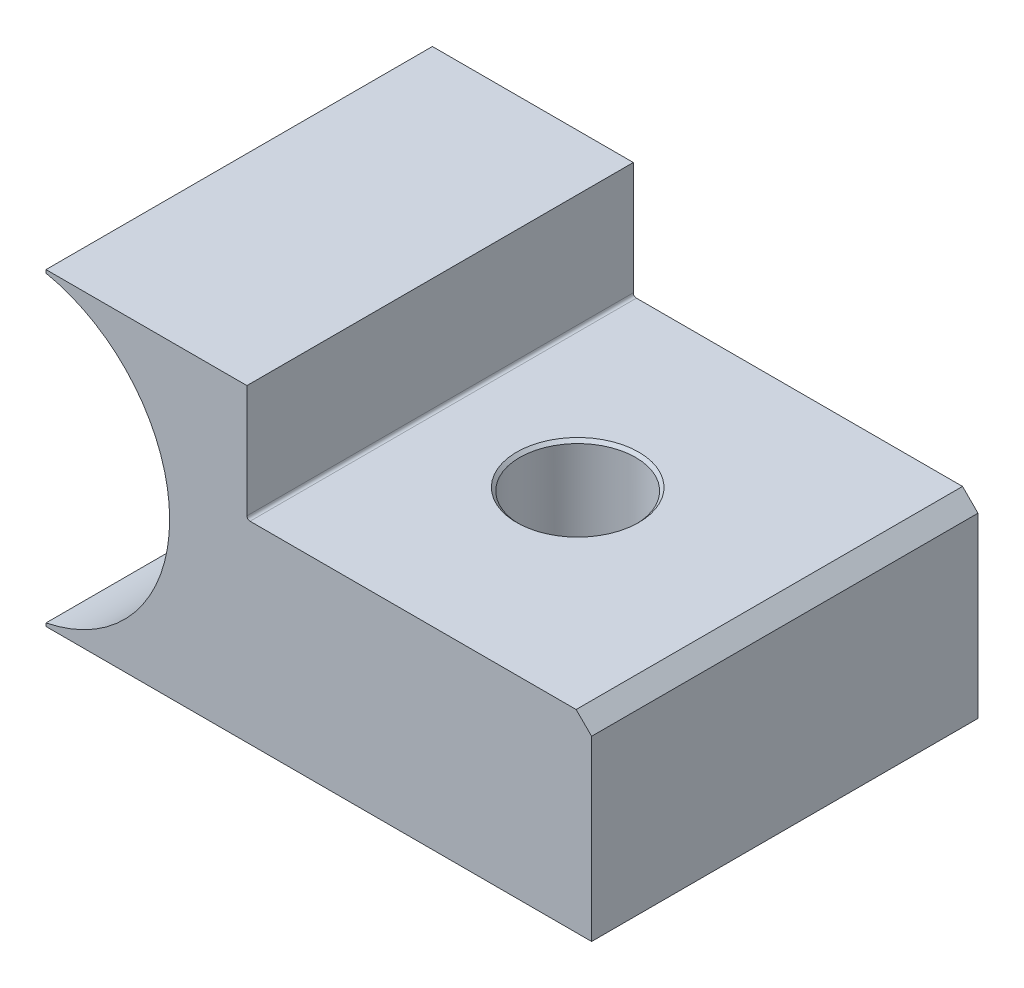
SolidWorks part; units mm, degrees
material "AISI Type A2 Tool Steel Custom"
ref_plane "Front Plane" through (0, 0, 0) normal (0, 0, 1) x (1, 0, 0)
ref_plane "Top Plane" through (0, 0, 0) normal (0, 1, 0) x (1, 0, 0)
ref_plane "Right Plane" through (0, 0, 0) normal (1, 0, 0) x (0, 0, -1)
sketch "Sketch1" plane through (0, 0, 0) normal (0, 0, 1) x (1, 0, 0)
  line L1 (2.54, 0) -> (47.371, 0)
  line L3 (2.54, 25.4) -> (19.05, 25.4)
  line L4 (47.371, 0) -> (47.371, 15.875)
  line L5 (2.54, 25.4) -> (2.54, 25.1434)
  line L6 (19.05, 25.4) -> (19.05, 15.875)
  line L7 (19.05, 15.875) -> (47.371, 15.875)
  line L8 (2.54, 0.2566) -> (2.54, 0)
  arc A1 (2.54, 0.2566) -> (2.54, 25.1434) centre (0, 12.7) ccw
  dimension "D2" = 25.4
  dimension "D1" = 16.51
  dimension "D3" = 9.525
  dimension "D4" = 2.54
  dimension "D5" = 28.321
  dimension "D6" = 15.875
  dimension "D7" = 0.2566
extrude "Boss-Extrude1" add sketch "Sketch1" along normal blind 31.75
sketch "Sketch2" plane through (0, 15.875, 0) normal (0, 1, 0) x (1, 0, 0)
  line L0 (0, -31.75) -> (0, 0) construction
  line L1 (2.54, -31.75) -> (2.54, 0) construction
  point P0 (30.353, -15.875)
  point P5 (0, -15.875)
  point P8 (2.54, -15.875)
  dimension "D1" = 30.353
hole_wizard "3/8 (0.375) Diameter Hole1" positions "Sketch2" profile "Sketch4" hole size "3/8" standard "ANSI Inch" end condition through all
sketch "Sketch4" plane through (30.353, 15.875, 15.875) normal (1, 0, 0) x (0, 0, 1)
  line L0 (0, 0) -> (0, 15.875)
  line L1 (0, 15.875) -> (4.7625, 15.875)
  line L2 (4.7625, 15.875) -> (4.7625, 0)
  line L5 (4.7625, 0) -> (0, 0)
  line L11 (0, -6.35) -> (0, 107.95) construction
  dimension "Thru Hole Dia." = 9.525
  dimension "Thru Hole Depth" = 15.875
chamfer "Chamfer1" distance 1.27 angle 45 1 edges at (47.371, 15.875, 15.875)
chamfer "Chamfer2" distance 0.254 angle 45 1 edges at (30.353, 15.875, 20.6375)
fillet "Fillet1" radius 0.254 1 edges at (19.05, 15.875, 15.875)
